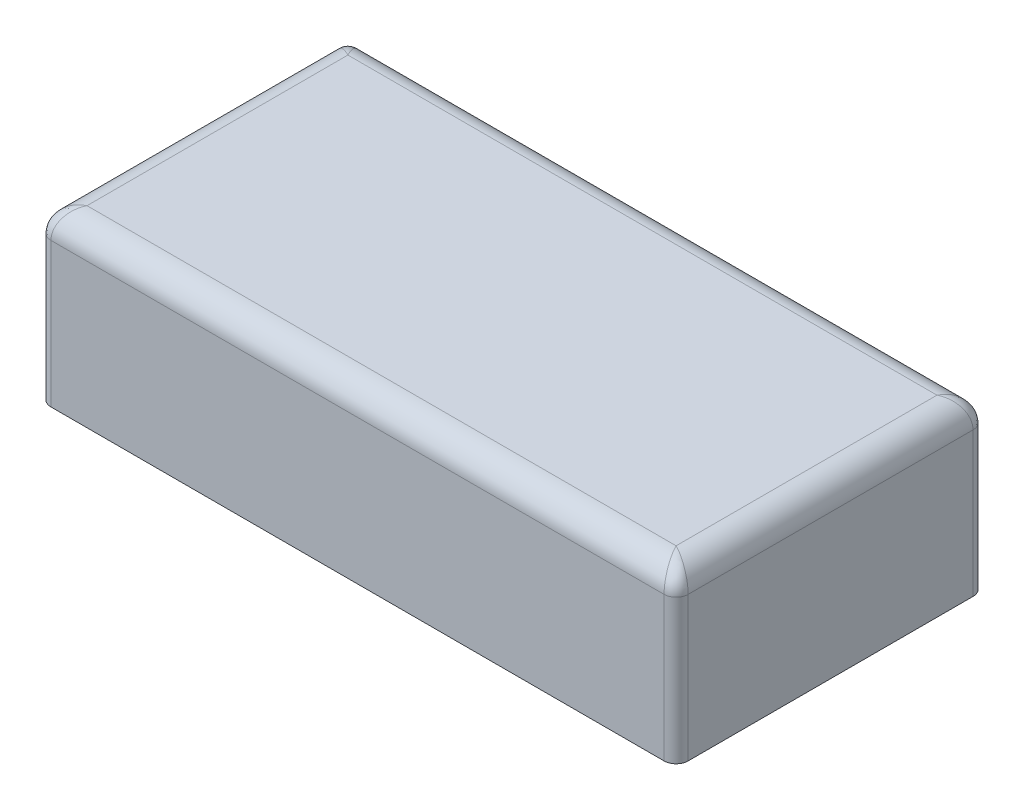
SolidWorks part; units mm, degrees
ref_plane "Front Plane" through (0, 0, 0) normal (0, 0, 1) x (1, 0, 0)
ref_plane "Top Plane" through (0, 0, 0) normal (0, 1, 0) x (1, 0, 0)
ref_plane "Right Plane" through (0, 0, 0) normal (1, 0, 0) x (0, 0, -1)
sketch "Sketch1" plane through (0, 0, 0) normal (0, 1, 0) x (1, 0, 0)
  line L1 (-64.3232, 35.5536) -> (70.2968, 35.5536)
  line L2 (-64.3232, 35.5536) -> (-64.3232, -29.7244)
  line L3 (-64.3232, -29.7244) -> (70.2968, -29.7244)
  line L4 (70.2968, 35.5536) -> (70.2968, -29.7244)
  dimension "D1" = 134.62
  dimension "D2" = 65.278
extrude "Boss-Extrude1" add sketch "Sketch1" along normal blind 35.56
sketch "Sketch5" plane through (0, 0, 0) normal (0, -1, 0) x (1, 0, 0)
  line L0 (-64.3232, 29.7244) -> (70.2968, 29.7244) construction
  line L1 (-61.1482, 26.5494) -> (67.1218, 26.5494)
  line L2 (-61.1482, 26.5494) -> (-61.1482, -32.3786)
  line L3 (-61.1482, -32.3786) -> (67.1218, -32.3786)
  line L4 (67.1218, 26.5494) -> (67.1218, -32.3786)
  line L5 (-64.3232, -35.5536) -> (-64.3232, 29.7244) construction
  dimension "D1" = 128.27
  dimension "D2" = 58.928
  dimension "D3" = 3.175
  dimension "D4" = 3.175
extrude "Cut-Extrude1" cut sketch "Sketch5" against normal blind 32.258
sketch "Sketch6" plane through (0, 0, 0) normal (0, -1, 0) x (1, 0, 0)
  line L0 (-64.3232, -35.5536) -> (-64.3232, 29.7244) construction
  line L1 (-63.0532, 28.4544) -> (69.0268, 28.4544)
  line L2 (-63.0532, 28.4544) -> (-63.0532, -34.2836)
  line L3 (-63.0532, -34.2836) -> (69.0268, -34.2836)
  line L4 (69.0268, 28.4544) -> (69.0268, -34.2836)
  line L5 (-64.3232, 29.7244) -> (70.2968, 29.7244) construction
  dimension "D1" = 132.08
  dimension "D2" = 62.738
  dimension "D3" = 1.27
  dimension "D4" = 1.27
extrude "Cut-Extrude2" cut sketch "Sketch6" against normal blind 5.588
sketch "Sketch7" plane through (-64.3232, 0, 0) normal (-1, 0, 0) x (0, 0, 1)
  line L0 (-35.5536, 0) -> (29.7244, 0) construction
  line L1 (-31.4896, 21.59) -> (25.6604, 21.59)
  line L2 (-31.4896, 21.59) -> (-31.4896, 0)
  line L3 (-31.4896, 0) -> (25.6604, 0)
  line L4 (25.6604, 21.59) -> (25.6604, 0)
  line L5 (-35.5536, 35.56) -> (-35.5536, 0) construction
  dimension "D1" = 57.15
  dimension "D2" = 4.064
  dimension "D3" = 21.59
extrude "Cut-Extrude3" cut sketch "Sketch7" against normal blind 5.588
sketch "Sketch8" plane through (0, 0, -35.5536) normal (0, 0, -1) x (-1, 0, 0)
  line L0 (-70.2968, 0) -> (64.3232, 0) construction
  line L1 (35.1132, 0) -> (-37.2768, 0)
  line L2 (35.1132, 0) -> (35.1132, 15.24)
  line L3 (35.1132, 15.24) -> (-37.2768, 15.24)
  line L4 (-37.2768, 0) -> (-37.2768, 15.24)
  line L5 (64.3232, 35.56) -> (64.3232, 0) construction
  dimension "D1" = 29.21
  dimension "D2" = 101.6
  dimension "D3" = 15.24
extrude "Cut-Extrude4" cut sketch "Sketch8" against normal blind 5.588
fillet "Fillet3" radius 5.08 4 edges at (2.9868, 35.56, -35.5536) (-64.3232, 35.56, -2.9146) (2.9868, 35.56, 29.7244) (70.2968, 35.56, -2.9146)
fillet "Fillet4" radius 2.54 8 edges at (68.8089, 34.0721, -34.0657) (68.8089, 34.0721, 28.2365) (-62.8353, 34.0721, 28.2365) (-62.8353, 34.0721, -34.0657) (70.2968, 15.24, -35.5536) (70.2968, 15.24, 29.7244) (-64.3232, 15.24, 29.7244) (-64.3232, 15.24, -35.5536)
fillet "Fillet5" radius 0.635 6 edges at (-64.3232, 10.795, 25.6604) (-64.3232, 21.59, -2.9146) (-64.3232, 10.795, -31.4896) (-35.1132, 7.62, -35.5536) (37.2768, 7.62, -35.5536) (1.0818, 15.24, -35.5536)
